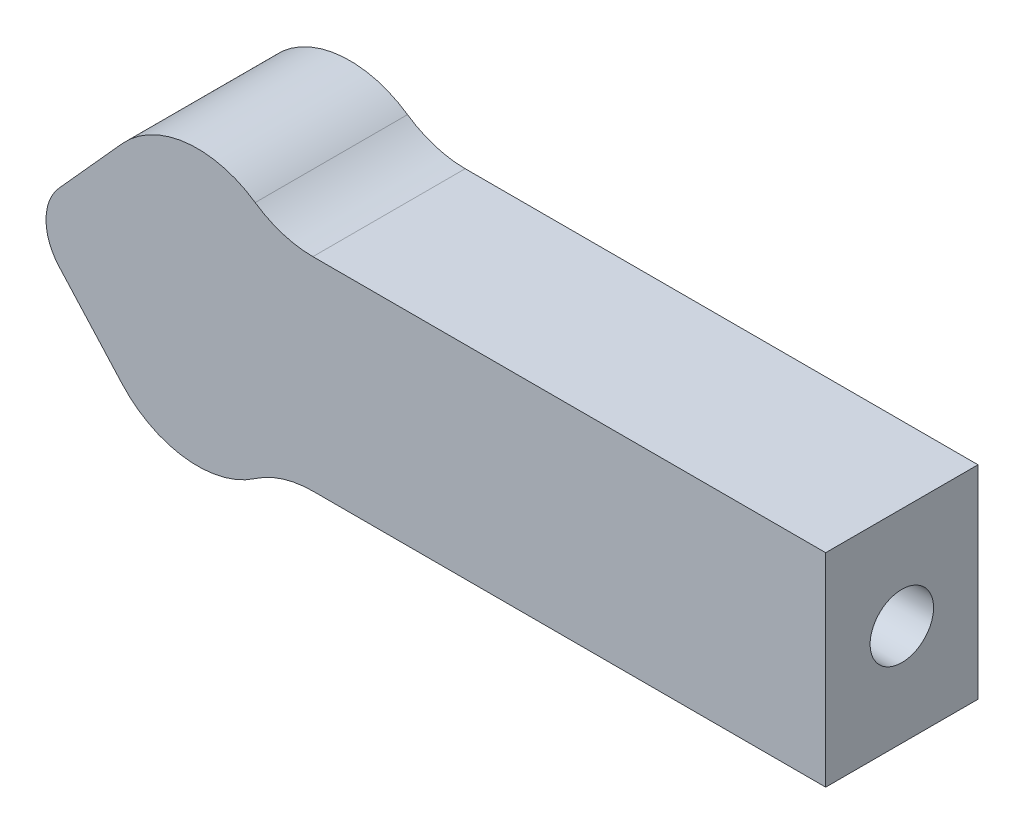
SolidWorks part; units mm, degrees
material "6061-T6 (SS)"
ref_plane "Front Plane" through (0, 0, 0) normal (0, 0, 1) x (1, 0, 0)
ref_plane "Top Plane" through (0, 0, 0) normal (0, 1, 0) x (1, 0, 0)
ref_plane "Right Plane" through (0, 0, 0) normal (1, 0, 0) x (0, 0, -1)
sketch "Sketch1" plane through (0, 0, 0) normal (0, 0, 1) x (1, 0, 0)
  line L0 (-3.05, 4) -> (-6.05, 0.6693)
  line L5 (-4.1825, -2.7426) -> (-3.05, -2) construction
  line L6 (-4.1825, 2.7426) -> (-3.05, 2) construction
  line L7 (-6.05, 0.6693) -> (-3.0711, -2.0138) construction
  line L8 (-6.05, -0.6693) -> (-3.05, -4)
  line L9 (-6.05, -0.6693) -> (-3.0711, 2.0138) construction
  line L10 (9.05, 2) -> (9.05, -2)
  line L15 (-3.05, 2) -> (-3.05, 4)
  line L16 (3.05, -2) -> (-3.05, -2)
  line L17 (-3.05, -2) -> (-3.05, -4)
  line L19 (3.05, 2) -> (-3.05, 2)
  line L21 (3.05, -2) -> (-3.05, 2) construction
  line L22 (3.05, 2) -> (-3.05, -2) construction
  line L23 (3.05, 2) -> (9.05, 2)
  line L25 (3.05, -2) -> (9.05, -2)
  arc A0 (-6.05, 0.6693) -> (-6.05, -0.6693) centre (-5.307, 0) ccw
  point P0 (0, 0)
  point P1 (0, 0)
  dimension "D6" = 6
  dimension "D4" = 1
  dimension "D1" = 6.1
  dimension "D2" = 4
  dimension "D3" = 3
  dimension "D5" = 2
  dimension "D7" = 6.1
extrude "Boss-Extrude1" add sketch "Sketch1" along normal blind 3 contours L8 L0 region at (1.357, 0, 0)
fillet "Fillet2" radius 2 2 edges at (-3.05, -2, 1.5) (-3.05, 2, 1.5)
fillet "Fillet3" radius 2 2 edges at (-3.05, -4, 1.5) (-3.05, 4, 1.5)
sketch "Sketch2" plane through (9.05, 0, 0) normal (1, 0, 0) x (0, 0, -1)
  line L0 (-3, -2) -> (0, -2) construction
  point P0 (-1.5, 0)
  point P6 (-1.5, -2)
hole_wizard "M1.6 Tapped Hole1" positions "Sketch3" profile "Sketch4" tap size "M1.6" standard "ISO"
sketch "Sketch3" plane through (9.05, 0, 0) normal (1, 0, 0) x (0, 0, -1)
  point P0 (-1.5, 0)
sketch "Sketch4" plane through (9.05, 0, 1.5) normal (0, 1, 0) x (0, 0, -1)
  line L0 (0, 0) -> (0, 3.3755)
  line L1 (0, 3.3755) -> (0.625, 3)
  line L2 (0.625, 3) -> (0.625, 0)
  line L5 (0.625, 0) -> (0, 0)
  line L10 (0, 3.3755) -> (-0.625, 3) construction
  line L11 (0, -6.35) -> (0, 107.95) construction
  dimension "Tap Drill Dia." = 1.25
  dimension "Tap Drill Depth" = 3
  dimension "Drill Angle" = 118
cosmetic thread "Hole Thread1" parameters "D1"=3, "D2"=1.6
